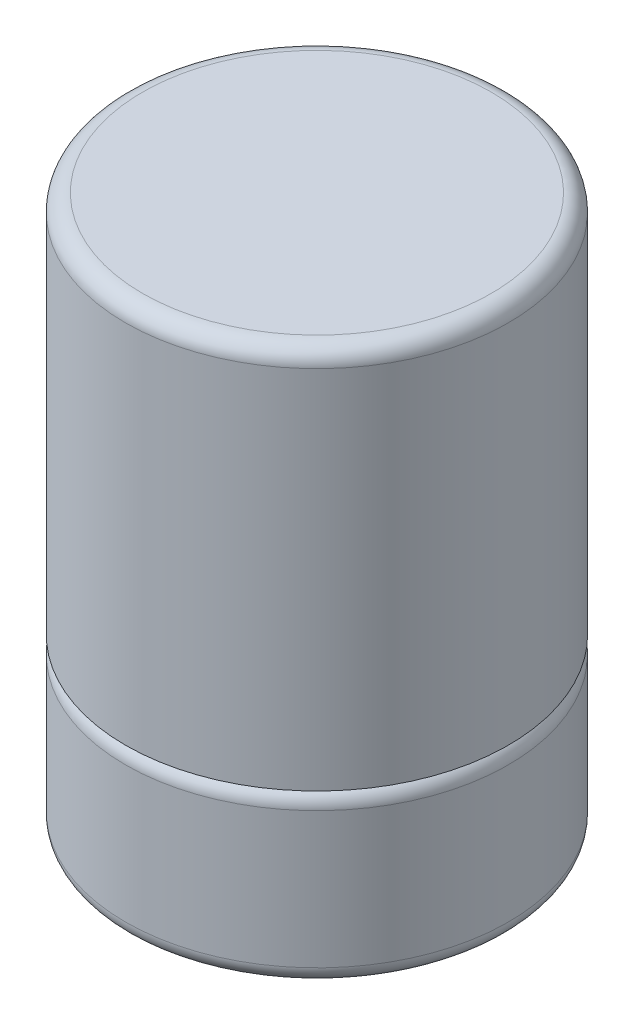
SolidWorks part; units mm, degrees
ref_plane "Front Plane" through (0, 0, 0) normal (0, 0, 1) x (1, 0, 0)
ref_plane "Top Plane" through (0, 0, 0) normal (0, 1, 0) x (1, 0, 0)
ref_plane "Right Plane" through (0, 0, 0) normal (1, 0, 0) x (0, 0, -1)
sketch "Sketch1" plane through (0, 0, 0) normal (0, 1, 0) x (1, 0, 0)
  circle A0 centre (0, 0) radius 14.2875
  dimension "D1" = 28.575
extrude "Boss-Extrude1" add sketch "Sketch1" along normal blind 12.7
fillet "Fillet1" radius 1.27 2 edges at (0, 0, 14.2875) (0, 12.7, 14.2875)
sketch "Sketch3" plane through (0, 12.7, 0) normal (0, 1, 0) x (1, 0, 0)
  circle A0 centre (0, 0) radius 14.2875
extrude "Boss-Extrude2" add sketch "Sketch3" along normal blind 28.575
fillet "Fillet2" radius 1.27 1 edges at (0, 41.275, 14.2875)
